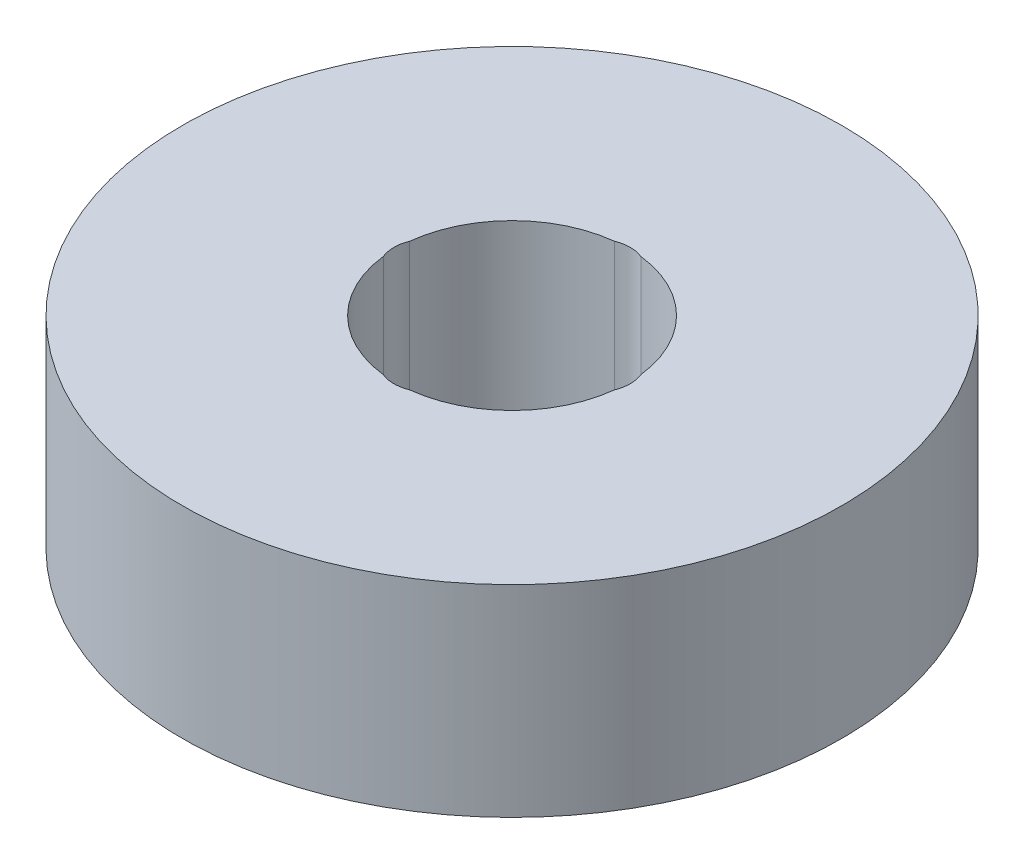
SolidWorks part; units mm, degrees
ref_plane "Front Plane" through (0, 0, 0) normal (0, 0, 1) x (1, 0, 0)
ref_plane "Top Plane" through (0, 0, 0) normal (0, 1, 0) x (1, 0, 0)
ref_plane "Right Plane" through (0, 0, 0) normal (1, 0, 0) x (0, 0, -1)
sketch "Sketch1" plane through (0, 0, 0) normal (0, 1, 0) x (1, 0, 0)
  circle A0 centre (0, 0) radius 42.5
  dimension "FLANGE_OD" = 85
extrude "Boss-Extrude1" add sketch "Sketch1" along normal blind 26
sketch "Sketch2" plane through (0, 0, 0) normal (0, 1, 0) x (1, 0, 0)
  circle A0 centre (0, 0) radius 15
  dimension "BORE_D" = 30
extrude "Cut-Extrude1" cut sketch "Sketch2" along normal through all
sketch "Sketch3" plane through (0, 26, 0) normal (0, 1, 0) x (1, 0, 0)
  circle A0 centre (0, 0) radius 10.7442 construction
  circle A1 centre (-10.7442, 0) radius 4.4939
  dimension "BOLT_D" = 8.9879
  dimension "BOLT_PCD" = 21.4883
extrude "Cut-Extrude2" cut sketch "Sketch3" against normal blind 25.3957
pattern_circular "CirPattern1" count 4 over 360 about axis through (0, 0, 0) along (0, 1, 0) of "Cut-Extrude2"
